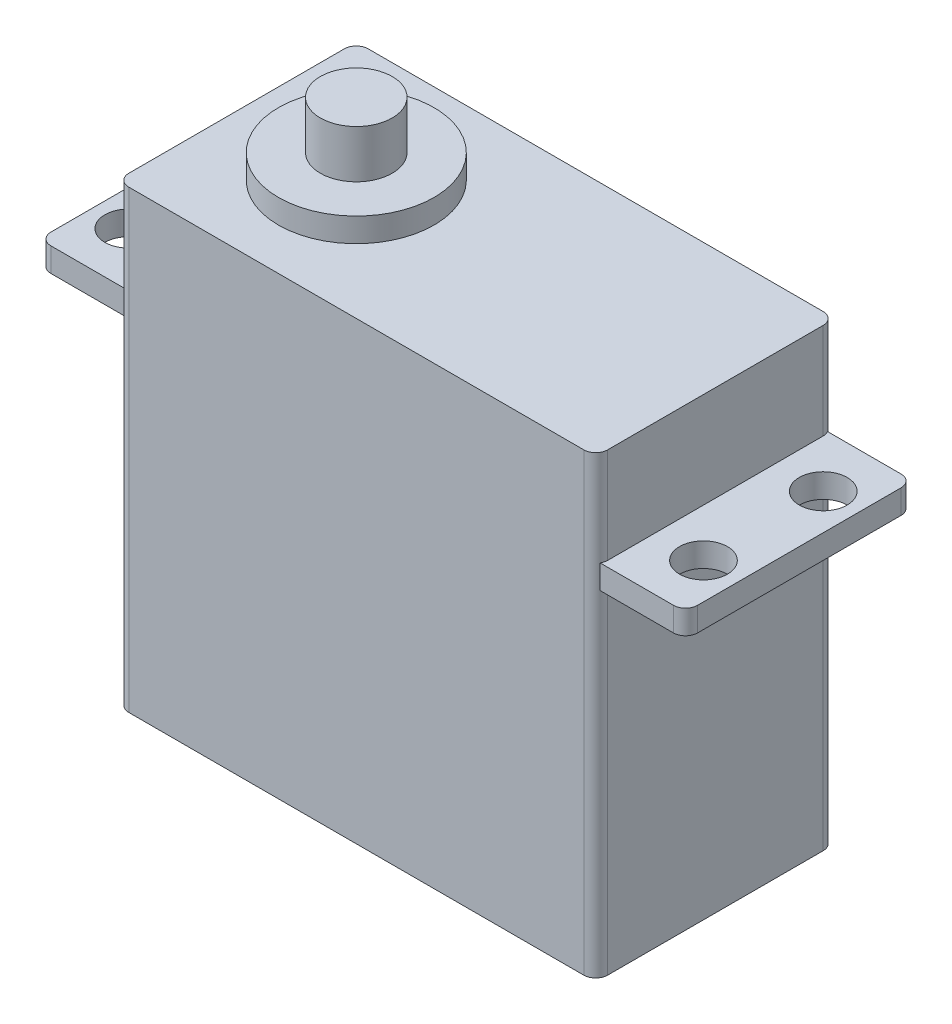
SolidWorks part; units mm, degrees
ref_plane "Спереди" through (0, 0, 0) normal (0, 0, 1) x (1, 0, 0)
ref_plane "Сверху" through (0, 0, 0) normal (0, 1, 0) x (1, 0, 0)
ref_plane "Справа" through (0, 0, 0) normal (1, 0, 0) x (0, 0, -1)
sketch "Эскиз1" plane through (0, 0, 0) normal (0, 1, 0) x (1, 0, 0)
  line L0 (-10, 0) -> (30, 0) construction
  line L1 (-10, 10) -> (30, 10)
  line L2 (-10, 10) -> (-10, -10)
  line L3 (-10, -10) -> (30, -10)
  line L4 (30, 10) -> (30, -10)
  line L5 (0, 10) -> (0, -10) construction
  dimension "D1" = 10
  dimension "D2" = 30
  dimension "D3" = 20
extrude "тело" add sketch "Эскиз1" against normal blind 38
sketch "Эскиз2" plane through (0, 0, 0) normal (0, 1, 0) x (1, 0, 0)
  circle A0 centre (0, 0) radius 6.5
  dimension "D1" = 13
extrude "выступ оси" add sketch "Эскиз2" along normal blind 2
sketch "Эскиз3" plane through (0, 2, 0) normal (0, 1, 0) x (1, 0, 0)
  circle A0 centre (0, 0) radius 3
  dimension "D1" = 6
extrude "ось" add sketch "Эскиз3" along normal blind 4
sketch "Эскиз4" plane through (30, 0, 0) normal (1, 0, 0) x (0, 0, -1)
  line L1 (-9.5, -8) -> (9.5, -8)
  line L2 (-9.5, -8) -> (-9.5, -10)
  line L3 (-9.5, -10) -> (9.5, -10)
  line L4 (9.5, -8) -> (9.5, -10)
  line L6 (-10, 0) -> (10, 0) construction
  line L7 (0, 0) -> (0, -38) construction
  line L8 (-10, -38) -> (10, -38) construction
  point P4 (0, -8)
  dimension "D1" = 2
  dimension "D2" = 8
  dimension "D3" = 19
extrude "крепления 1" add sketch "Эскиз4" along normal blind 7
sketch "Эскиз6" plane through (-10, 0, 0) normal (-1, 0, 0) x (0, 0, 1)
  line L1 (-9.5, -8) -> (9.5, -8)
  line L2 (-9.5, -8) -> (-9.5, -10)
  line L3 (-9.5, -10) -> (9.5, -10)
  line L4 (9.5, -8) -> (9.5, -10)
  line L6 (-10, 0) -> (10, 0) construction
  line L7 (0, 0) -> (0, -38) construction
  line L8 (-10, -38) -> (10, -38) construction
  point P5 (0, -8)
  dimension "D1" = 2
  dimension "D2" = 8
  dimension "D3" = 19
extrude "крепления 2" add sketch "Эскиз6" along normal blind 7
sketch "Эскиз7" plane through (0, -8, 0) normal (0, 1, 0) x (1, 0, 0)
  line L0 (30, 0) -> (37, 0) construction
  line L1 (30, 9.5) -> (30, -9.5) construction
  line L2 (37, 9.5) -> (37, -9.5) construction
  circle A0 centre (34, 5) radius 2
  circle A1 centre (34, -5) radius 2
  dimension "D1" = 4
  dimension "D3" = 10
  dimension "D2" = 3
extrude "отверстия 1" cut sketch "Эскиз7" against normal through all
sketch "Эскиз8" plane through (0, -8, 0) normal (0, 1, 0) x (1, 0, 0)
  line L0 (-17, 0) -> (-10, 0) construction
  line L1 (-17, -9.5) -> (-17, 9.5) construction
  line L2 (-10, 10) -> (-10, -10) construction
  circle A0 centre (-14, 5) radius 2
  circle A1 centre (-14, -5) radius 2
  dimension "D1" = 3
  dimension "D2" = 10
  dimension "D3" = 4
extrude "отверстия 2" cut sketch "Эскиз8" against normal through all
sketch "Эскиз9" plane through (-10, 0, 0) normal (-1, 0, 0) x (0, 0, 1)
  line L0 (0, 0) -> (0, -38) construction
  line L1 (-10, -38) -> (10, -38) construction
  line L2 (-3, -33) -> (3, -33) construction
  line L3 (-3, -31) -> (3, -31)
  line L4 (-3, -31) -> (-3, -35)
  line L5 (-3, -35) -> (3, -35)
  line L6 (3, -31) -> (3, -35)
  point P11 (0, -33)
  dimension "D1" = 7
  dimension "D2" = 6
  dimension "D3" = 4
extrude "выступ проводов" add sketch "Эскиз9" along normal blind 3
fillet "Скругление1" radius 1 8 edges at (30, -19, 10) (30, -19, -10) (37, -9, -9.5) (37, -9, 9.5) (-17, -9, -9.5) (-10, -19, 10) (-17, -9, 9.5) (-10, -19, -10)
